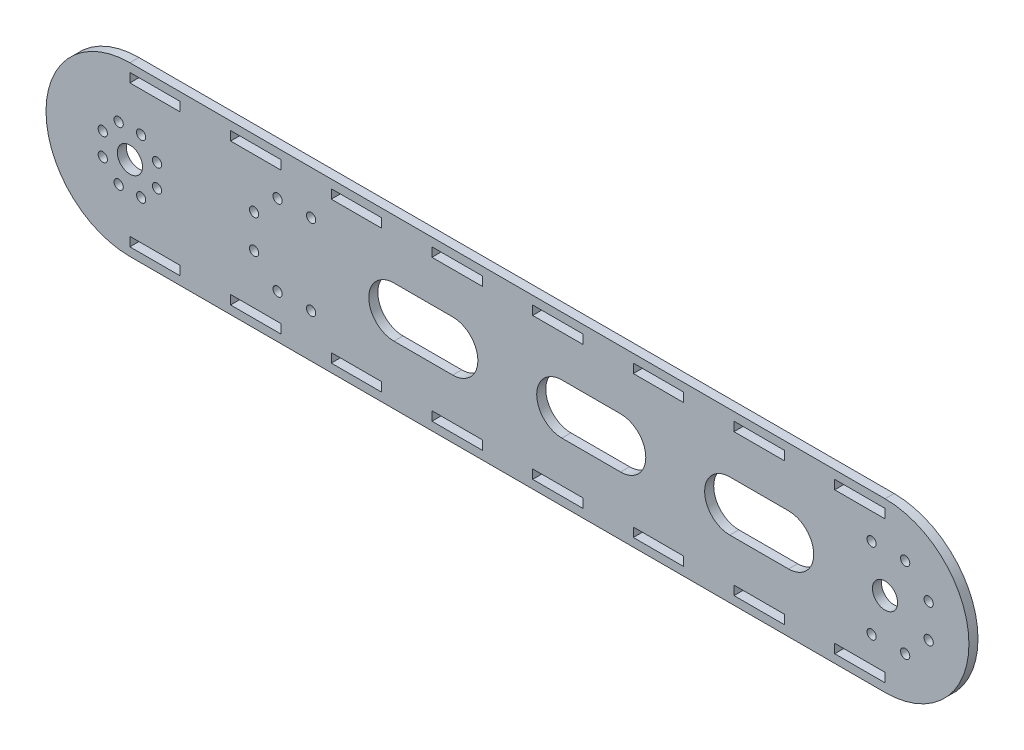
SolidWorks part; units mm, degrees
ref_plane "Front Plane" through (0, 0, 0) normal (0, 0, 1) x (1, 0, 0)
ref_plane "Top Plane" through (0, 0, 0) normal (0, 1, 0) x (1, 0, 0)
ref_plane "Right Plane" through (0, 0, 0) normal (1, 0, 0) x (0, 0, -1)
sketch "Sketch3" plane through (0, 0, 0) normal (0, 0, 1) x (1, 0, 0)
  line L0 (-242.5, 0) -> (207.5, 0) construction
  line L1 (-242.5, 50) -> (207.5, 50)
  line L2 (-242.5, -50) -> (207.5, -50)
  line L6 (115, 0) -> (150, 0) construction
  line L7 (115, 15) -> (150, 15)
  line L8 (115, -15) -> (150, -15)
  line L9 (-242.5, 0) -> (-226.3321, 6.697)
  line L10 (-242.5, 0) -> (-226.3321, 6.697) construction
  line L11 (-242.5, 0) -> (-226.3321, -6.697) construction
  line L36 (-101.4371, 0) -> (436.7316, 0) construction
  line L64 (-242.5, 45) -> (-212.5, 45)
  line L67 (-212.5, 45) -> (-212.5, 39.6)
  line L69 (32.5, 50) -> (32.5, -50) construction
  line L71 (-182.5, 45) -> (-152.5, 45)
  line L72 (-242.5, 39.6) -> (-212.5, 39.6)
  line L73 (-152.5, 45) -> (-152.5, 39.6)
  line L74 (14.924, 0) -> (49.924, 0) construction
  line L75 (14.924, 15) -> (49.924, 15)
  line L78 (14.924, -15) -> (49.924, -15)
  line L79 (-85.152, 0) -> (-50.152, 0) construction
  line L80 (-85.152, 15) -> (-50.152, 15)
  line L81 (-85.152, -15) -> (-50.152, -15)
  line L82 (-242.5, 45) -> (-242.5, 39.6)
  line L91 (-292.5, 0) -> (-17.5, 0) construction
  line L96 (-182.5, 39.6) -> (-152.5, 39.6)
  line L97 (-182.5, 45) -> (-182.5, 39.6)
  line L98 (-122.5, 45) -> (-92.5, 45)
  line L99 (-92.5, 45) -> (-92.5, 39.6)
  line L100 (-122.5, 39.6) -> (-92.5, 39.6)
  line L101 (-122.5, 45) -> (-122.5, 39.6)
  line L102 (-62.5, 45) -> (-32.5, 45)
  line L103 (-32.5, 45) -> (-32.5, 39.6)
  line L104 (-62.5, 39.6) -> (-32.5, 39.6)
  line L105 (-62.5, 45) -> (-62.5, 39.6)
  line L106 (-2.5, 45) -> (27.5, 45)
  line L107 (27.5, 45) -> (27.5, 39.6)
  line L108 (-2.5, 39.6) -> (27.5, 39.6)
  line L109 (-2.5, 45) -> (-2.5, 39.6)
  line L110 (57.5, 45) -> (87.5, 45)
  line L111 (87.5, 45) -> (87.5, 39.6)
  line L112 (57.5, 39.6) -> (87.5, 39.6)
  line L113 (57.5, 45) -> (57.5, 39.6)
  line L114 (117.5, 45) -> (147.5, 45)
  line L115 (147.5, 45) -> (147.5, 39.6)
  line L116 (117.5, 39.6) -> (147.5, 39.6)
  line L117 (117.5, 45) -> (117.5, 39.6)
  line L118 (177.5, 45) -> (207.5, 45)
  line L119 (207.5, 45) -> (207.5, 39.6)
  line L120 (177.5, 39.6) -> (207.5, 39.6)
  line L121 (177.5, 45) -> (177.5, 39.6)
  line L122 (177.5, -45) -> (177.5, -39.6)
  line L123 (177.5, -39.6) -> (207.5, -39.6)
  line L124 (207.5, -45) -> (207.5, -39.6)
  line L125 (177.5, -45) -> (207.5, -45)
  line L126 (117.5, -45) -> (117.5, -39.6)
  line L127 (117.5, -39.6) -> (147.5, -39.6)
  line L128 (147.5, -45) -> (147.5, -39.6)
  line L129 (117.5, -45) -> (147.5, -45)
  line L130 (57.5, -45) -> (57.5, -39.6)
  line L131 (57.5, -39.6) -> (87.5, -39.6)
  line L132 (87.5, -45) -> (87.5, -39.6)
  line L133 (57.5, -45) -> (87.5, -45)
  line L134 (-2.5, -45) -> (-2.5, -39.6)
  line L135 (-2.5, -39.6) -> (27.5, -39.6)
  line L136 (27.5, -45) -> (27.5, -39.6)
  line L137 (-2.5, -45) -> (27.5, -45)
  line L138 (-62.5, -45) -> (-62.5, -39.6)
  line L139 (-62.5, -39.6) -> (-32.5, -39.6)
  line L140 (-32.5, -45) -> (-32.5, -39.6)
  line L141 (-62.5, -45) -> (-32.5, -45)
  line L142 (-122.5, -45) -> (-122.5, -39.6)
  line L143 (-122.5, -39.6) -> (-92.5, -39.6)
  line L144 (-92.5, -45) -> (-92.5, -39.6)
  line L145 (-122.5, -45) -> (-92.5, -45)
  line L146 (-182.5, -45) -> (-182.5, -39.6)
  line L147 (-182.5, -39.6) -> (-152.5, -39.6)
  line L148 (-152.5, -45) -> (-152.5, -39.6)
  line L149 (-182.5, -45) -> (-152.5, -45)
  line L150 (-242.5, -45) -> (-242.5, -39.6)
  line L151 (-242.5, -39.6) -> (-212.5, -39.6)
  line L152 (-212.5, -45) -> (-212.5, -39.6)
  line L153 (-242.5, -45) -> (-212.5, -45)
  arc A0 (-242.5, 50) -> (-242.5, -50) centre (-242.5, 0) ccw
  arc A1 (207.5, -50) -> (207.5, 50) centre (207.5, 0) ccw
  circle A2 centre (-242.5, 0) radius 7.5
  circle A3 centre (207.5, 0) radius 7.5
  arc A6 (115, 15) -> (115, -15) centre (115, 0) ccw
  arc A7 (150, -15) -> (150, 15) centre (150, 0) ccw
  circle A8 centre (-226.3321, 6.697) radius 2.75
  circle A9 centre (-226.3321, -6.697) radius 2.75
  circle A10 centre (-235.803, -16.1679) radius 2.75
  circle A11 centre (-249.197, -16.1679) radius 2.75
  circle A12 centre (-258.6679, -6.697) radius 2.75
  circle A13 centre (-258.6679, 6.697) radius 2.75
  circle A14 centre (-249.197, 16.1679) radius 2.75
  circle A15 centre (-235.803, 16.1679) radius 2.75
  circle A41 centre (-134.5, -24) radius 2.75
  circle A42 centre (-154.5, -24) radius 2.75
  circle A43 centre (-168.5, -10) radius 2.75
  circle A44 centre (-168.5, 10) radius 2.75
  circle A45 centre (-154.5, 24) radius 2.75
  circle A46 centre (-134.5, 24) radius 2.75
  arc A49 (14.924, 15) -> (14.924, -15) centre (14.924, 0) ccw
  arc A50 (49.924, -15) -> (49.924, 15) centre (49.924, 0) ccw
  arc A51 (-85.152, 15) -> (-85.152, -15) centre (-85.152, 0) ccw
  arc A52 (-50.152, -15) -> (-50.152, 15) centre (-50.152, 0) ccw
  circle A53 centre (199.5, -24) radius 2.75
  circle A54 centre (219.5, -24) radius 2.75
  circle A55 centre (233.5, -10) radius 2.75
  circle A56 centre (233.5, 10) radius 2.75
  circle A57 centre (219.5, 24) radius 2.75
  circle A58 centre (199.5, 24) radius 2.75
  point P3 (-17.5, 0)
  point P19 (132.5, 0)
  point P68 (32.424, 0)
  point P75 (-67.652, 0)
  dimension "D2" = 50
  dimension "D3" = 15
  dimension "D4" = 15
  dimension "D7" = 5.5
  dimension "D27" = 15
  dimension "D1" = 450
  dimension "D5" = 17.5
  dimension "D6" = 22.5
  dimension "D9" = 45
  dimension "D10" = 0
  dimension "D11" = 5
  dimension "D12" = 8
  dimension "D15" = 3
  dimension "D26" = 35
  dimension "D29" = 150
  dimension "D30" = 175
  dimension "D13" = 5.4
  dimension "D8" = 8
extrude "Boss-Extrude1" add sketch "Sketch3" along normal blind 5.4 contours L2 A1 L1 A0 A58 A57 A56 A54 A46 A44 A43 A42 A41 A15 A14 A13 A12 A11 A10 A9 A8 A2 A7 L8 A6 L7 A3 L82 L64 region at (-22.8126, 0, 0)
